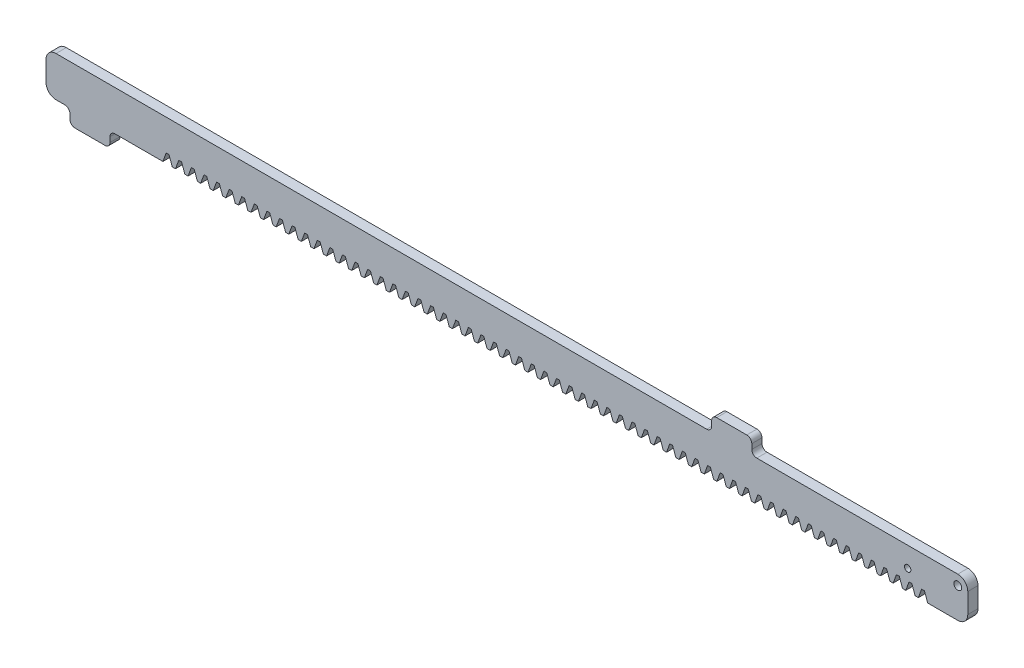
SolidWorks part; units mm, degrees
material "PC High Viscosity"
ref_plane "Front Plane" through (0, 0, 0) normal (0, 0, 1) x (1, 0, 0)
ref_plane "Top Plane" through (0, 0, 0) normal (0, 1, 0) x (1, 0, 0)
ref_plane "Right Plane" through (0, 0, 0) normal (1, 0, 0) x (0, 0, -1)
sketch "Sketch1" plane through (0, 0, 0) normal (0, 0, 1) x (1, 0, 0)
  line L1 (0, 0) -> (15.1307, 0)
  line L2 (0, 0) -> (0, 25.4)
  line L3 (0, 25.4) -> (40.5308, 25.4)
  line L4 (584.2, 0) -> (584.2, 25.4)
  line L7 (533.4, 25.4) -> (584.2, 25.4)
  line L8 (40.5308, 25.4) -> (421.9033, 25.4)
  line L9 (40.5307, 0) -> (584.2, 0)
  line L11 (584.2, 22.7162) -> (577.85, 26.3823) construction
  line L12 (577.85, 26.3823) -> (571.5, 22.7162) construction
  line L13 (571.5, 22.7162) -> (571.5, 15.3838) construction
  line L14 (571.5, 15.3838) -> (577.85, 11.7177) construction
  line L15 (577.85, 11.7177) -> (584.2, 15.3838) construction
  line L16 (584.2, 15.3838) -> (584.2, 22.7162) construction
  line L19 (590.55, 0) -> (590.55, 10.0162) construction
  line L20 (590.55, 10.0162) -> (76.2, 10.0162) construction
  line L21 (76.2, 10.0162) -> (76.2, 0) construction
  line L22 (447.3033, 25.4) -> (533.4, 25.4)
  line L26 (15.1307, 0) -> (15.1307, -9.525)
  line L27 (15.1307, -9.525) -> (40.5307, -9.525)
  line L28 (40.5307, -9.525) -> (40.5307, 0)
  line L29 (421.9033, 25.4) -> (421.9033, 34.925)
  line L30 (421.9033, 34.925) -> (447.3033, 34.925)
  line L31 (447.3033, 34.925) -> (447.3033, 25.4)
  circle A0 centre (577.85, 19.05) radius 2.4892
  circle A1 centre (577.85, 19.05) radius 6.35 construction
  dimension "D5" = 4.9784
  dimension "D6" = 40.5307
  dimension "D7" = 12.7
  dimension "D1" = 584.2
  dimension "D2" = 25.4
  dimension "D3" = 421.9033
  dimension "D4" = 9.525
  dimension "D8" = 25.4
  dimension "D9" = 25.4
extrude "Boss-Extrude1" add sketch "Sketch1" along normal blind 6.477 contours L3 | L1 L4 L3 L2 A0 | L1 region at (289.8115, 12.6919, 0)
fillet "Fillet2" radius 6.35 4 edges at (0, 0, 3.2385) (0, 25.4, 3.2385) (584.2, 25.4, 3.2385) (584.2, 0, 3.2385)
sketch "Sketch2" plane through (0, 0, 6.477) normal (0, 0, 1) x (1, 0, 0)
  line L0 (558.8, 0) -> (43.7057, 0)
  line L1 (43.7057, 0) -> (43.7057, 5.715)
  line L2 (43.7057, 5.715) -> (558.8, 5.715)
  line L3 (558.8, 5.715) -> (558.8, 0)
  line L5 (557.8755, 2.54) -> (549.711, 2.54) construction
  line L6 (558.8, 0) -> (556.7199, 5.715)
  line L7 (65.9307, 0) -> (578.2688, 0) construction
  line L8 (552.8688, 0) -> (558.8, 0)
  line L10 (556.7199, 5.715) -> (554.9488, 5.715)
  line L11 (558.8, 0) -> (552.8688, 0)
  line L12 (552.8688, 0) -> (554.9488, 5.715)
  line L13 (554.9488, 5.715) -> (556.7199, 5.715)
  line L14 (558.8, 0) -> (552.8688, 0)
  line L15 (554.9488, 5.715) -> (556.7199, 5.715)
  line L16 (558.8, 0) -> (552.8688, 0)
  line L17 (552.8688, 0) -> (558.8, 0)
  line L19 (556.7199, 5.715) -> (554.9488, 5.715) construction
  line L20 (552.8688, 0) -> (558.8, 0) construction
  line L21 (0, 0) -> (15.1307, 0) construction
  line L22 (584.2, 0) -> (584.2, 25.4) construction
  line L23 (40.5307, 0) -> (584.2, 0) construction
  point P8 (553.7932, 2.54)
  point P16 (557.8755, 2.54)
  dimension "D1" = 70
  dimension "D2" = 2.54
  dimension "D3" = 3.175
  dimension "D4" = 70
  dimension "D5" = 1.7711
  dimension "D6" = 25.4
extrude "Cut-Extrude1" cut sketch "Sketch2" against normal through all contours L12 L0 L8 L6 L2 region at (555.8344, 2.343, 6.477)
pattern_linear "LPattern1" count 61 spacing 7.9796 along (-1, 0, 0) of "Cut-Extrude1"
sketch "Sketch3" plane through (0, 0, 6.477) normal (0, 0, 1) x (1, 0, 0)
  line L2 (533.4, 25.4) -> (584.2, 25.4) construction
  line L3 (584.2, 0) -> (584.2, 25.4) construction
  circle A0 centre (546.1, 12.7) radius 2.0193
  dimension "D2" = 4.0386
  dimension "D1" = 12.7
  dimension "D3" = 38.1
extrude "Cut-Extrude2" cut sketch "Sketch3" against normal through all
fillet "Fillet3" radius 3.175 8 edges at (421.9033, 25.4, 3.2385) (421.9033, 34.925, 3.2385) (447.3033, 34.925, 3.2385) (447.3033, 25.4, 3.2385) (40.5307, -9.525, 3.2385) (40.5307, 0, 3.2385) (15.1307, -9.525, 3.2385) (15.1307, 0, 3.2385)
